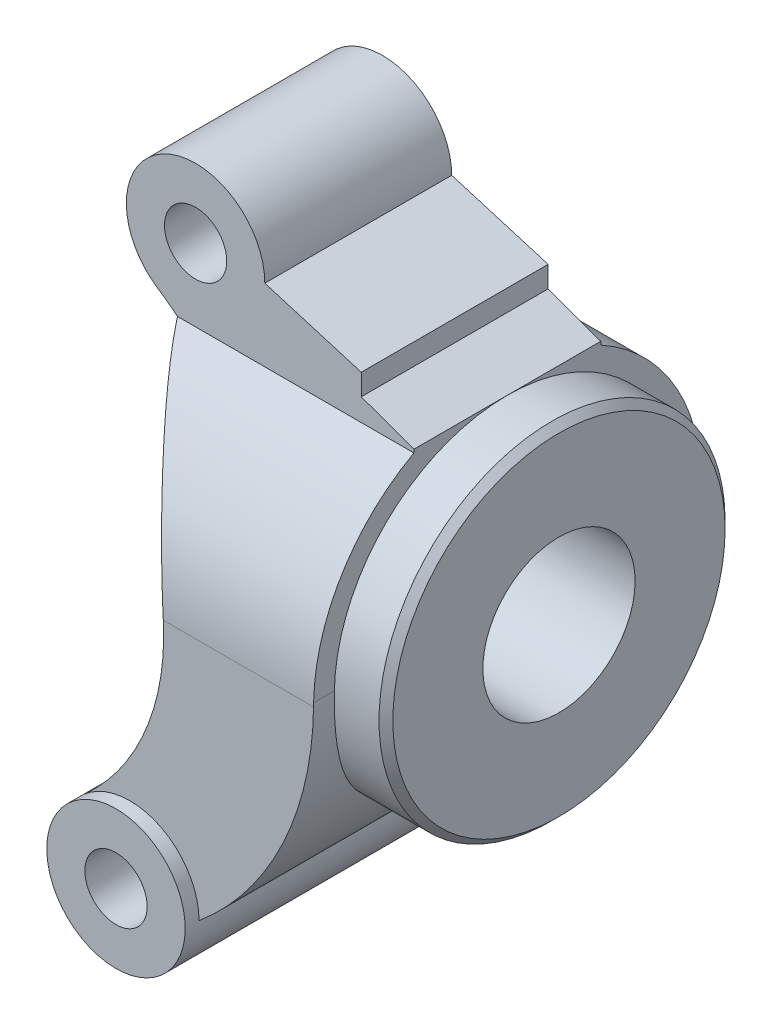
SolidWorks part; units mm, degrees
ref_plane "Front Plane" through (0, 0, 0) normal (0, 0, 1) x (1, 0, 0)
ref_plane "Top Plane" through (0, 0, 0) normal (0, 1, 0) x (1, 0, 0)
ref_plane "Right Plane" through (0, 0, 0) normal (1, 0, 0) x (0, 0, -1)
sketch "Sketch1" plane through (0, 0, 0) normal (1, 0, 0) x (0, 0, -1)
  circle A0 centre (0, 0) radius 39.6875
  dimension "D1" = 79.375
extrude "Extrude1" add sketch "Sketch1" along normal blind 20.6375 and the other way blind 20.6375
sketch "Sketch2" plane through (0, 0, 0) normal (0, 0, 1) x (1, 0, 0)
  line L0 (20.6375, -39.6875) -> (20.6375, 39.6875) construction
  line L1 (-20.6375, -39.6875) -> (20.6375, -39.6875) construction
  circle A0 centre (-33.3375, -55.5625) radius 15.875
  dimension "D1" = 31.75
  dimension "D2" = 53.975
extrude "Extrude2" add sketch "Sketch2" along normal blind 47.625 and the other way blind 47.625 separate body
sketch "Sketch3" plane through (0, 0, 0) normal (0, 0, 1) x (1, 0, 0)
  line L0 (20.6375, -39.6875) -> (20.6375, 39.6875) construction
  line L1 (20.6375, 39.6875) -> (-20.6375, 39.6875) construction
  circle A0 centre (-41.275, 55.5625) radius 15.875
  dimension "D1" = 31.75
  dimension "D2" = 61.9125
extrude "Extrude3" add sketch "Sketch3" along normal blind 21.4312 and the other way blind 21.4312 separate body
sketch "Sketch4" plane through (0, 0, 0) normal (0, 0, 1) x (1, 0, 0)
  line L0 (-79.8656, -3.04) -> (0, 0) construction
  line L1 (0, 0) -> (-20.6375, -39.6875) construction
  line L2 (-20.6375, -39.6875) -> (-79.8656, -3.04) construction
  line L3 (-50.0059, 42.304) -> (-25.4, 55.5625)
  line L4 (-25.4, 55.5625) -> (-3.2794, 48.9333)
  line L5 (-3.2794, 48.9333) -> (-3.2794, 44.0595)
  line L6 (-3.2794, 44.0595) -> (8.7979, 39.6875)
  line L7 (20.6375, 39.6875) -> (-20.6375, 39.6875) construction
  line L8 (8.7979, 39.6875) -> (8.7979, -39.6875)
  line L9 (-20.6375, -39.6875) -> (20.6375, -39.6875) construction
  line L10 (8.7979, -39.6875) -> (-17.4625, -55.5625)
  line L11 (-17.4625, -55.5625) -> (-43.8642, -43.6796)
  arc A0 (-43.8642, -43.6796) -> (-50.0059, 42.304) centre (-79.8656, -3.04) ccw
  circle A3 centre (-33.3375, -55.5625) radius 15.875 construction
  circle A4 centre (-41.275, 55.5625) radius 15.875 construction
  dimension "D1" = 79.8656
  dimension "D3" = 54.2925
  dimension "D2" = 69.6492
  dimension "D4" = 27.9506
  dimension "D5" = 22.1206
  dimension "D6" = 23.0926
  dimension "D7" = 12.8443
  dimension "D8" = 12.0773
  dimension "D9" = 30.6859
extrude "Extrude4" add sketch "Sketch4" along normal blind 44.45 and the other way blind 44.45
sketch "Sketch6" plane through (0, 0, 0) normal (1, 0, 0) x (0, 0, -1)
  line L2 (-21.4313, 55.5625) -> (-21.4313, 38.9423)
  line L3 (-44.45, -39.6875) -> (-44.45, 39.6875) construction
  line L4 (21.4312, 55.5625) -> (21.4312, 38.9423)
  line L5 (44.45, -39.6875) -> (44.45, 39.6875) construction
  line L7 (-21.4313, 55.5625) -> (-44.45, 55.5625)
  line L8 (-44.45, 55.5625) -> (-44.45, 0)
  line L9 (21.4312, 55.5625) -> (44.45, 55.5625)
  line L10 (44.45, 55.5625) -> (44.45, 0)
  arc A0 (-44.45, 0) -> (-21.4313, 38.9423) centre (0, 0) cw
  arc A1 (44.45, 0) -> (21.4312, 38.9423) centre (0, 0) ccw
extrude "Extrude5" cut sketch "Sketch6" against normal through all and the other way through all
sketch "Sketch7" plane through (20.6375, 0, 0) normal (1, 0, 0) x (0, 0, -1)
  circle A0 centre (0, 0) radius 17.4625
  dimension "D1" = 34.925
extrude "Extrude6" cut sketch "Sketch7" against normal through all
hole_wizard "9/16 (0.5625) Diameter Hole1" positions "Sketch9" profile "Sketch10" hole size "9/16" standard "Ansi Inch" end condition through all
sketch "Sketch9" plane through (0, 0, 47.625) normal (0, 0, 1) x (1, 0, 0)
  point P1 (-33.3375, -55.5625)
sketch "Sketch10" plane through (-33.3375, -55.5625, 47.625) normal (1, 0, 0) x (0, -1, 0)
  line L0 (0, 0) -> (0, 95.25)
  line L1 (0, 95.25) -> (7.1437, 95.25)
  line L2 (7.1437, 95.25) -> (7.1437, 0)
  line L5 (7.1437, 0) -> (0, 0)
  line L11 (0, -6.35) -> (0, 107.95) construction
  dimension "Thru Hole Dia." = 14.2875
  dimension "Thru Hole Depth" = 95.25
hole_wizard "9/16 (0.5625) Diameter Hole2" positions "Sketch12" profile "Sketch13" hole size "9/16" standard "Ansi Inch" end condition through all
sketch "Sketch12" plane through (0, 0, 21.4312) normal (0, 0, 1) x (1, 0, 0)
  point P1 (-41.275, 55.5625)
sketch "Sketch13" plane through (-41.275, 55.5625, 21.4312) normal (1, 0, 0) x (0, -1, 0)
  line L0 (0, 0) -> (0, 69.0563)
  line L1 (0, 69.0563) -> (7.1437, 69.0563)
  line L2 (7.1437, 69.0563) -> (7.1437, 0)
  line L5 (7.1437, 0) -> (0, 0)
  line L11 (0, -6.35) -> (0, 107.95) construction
  dimension "Thru Hole Dia." = 14.2875
  dimension "Thru Hole Depth" = 69.0563
chamfer "Chamfer1" distance 1.5875 angle 45 1 edges at (20.6375, 0, -39.6875)
fillet "Fillet1" radius 73.66 1 edges at (8.7979, -39.6875, 22.225)
